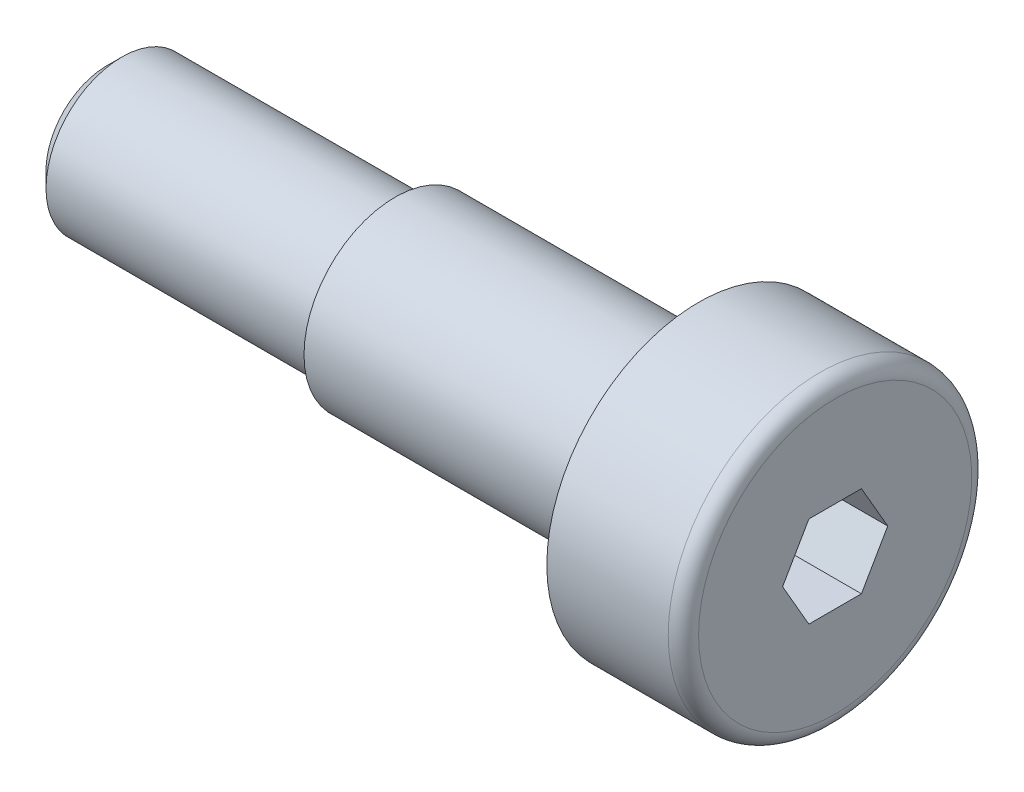
SolidWorks part; units mm, degrees
material "AISI 1020"
ref_plane "XY (Front)" through (0, 0, 0) normal (0, 0, 1) x (1, 0, 0)
ref_plane "XZ (Top)" through (0, 0, 0) normal (0, 1, 0) x (1, 0, 0)
ref_plane "YZ (Right)" through (0, 0, 0) normal (1, 0, 0) x (0, 0, -1)
ref_axis "X" through (-25.2, 0, 0) along (1, 0, 0)
ref_axis "Y" through (0, 5.5, 0) along (0, -1, 0)
ref_axis "Z" through (0, 0, -5.5) along (0, 0, 1)
sketch "Sketch1" plane through (0, 0, 0) normal (0, 0, 1) x (1, 0, 0)
  line L0 (0, 0) -> (0, 4.5)
  line L1 (-0.5, 5) -> (-4.5, 5)
  line L2 (-4.5, 5) -> (-4.5, 3)
  line L3 (-4.5, 3) -> (-14.5, 3)
  line L4 (-14.5, 3) -> (-14.5, 2.5)
  line L5 (-14.5, 2.5) -> (-24, 2.5)
  line L6 (-24, 2.5) -> (-24, 0)
  line L7 (-24, 0) -> (0, 0)
  line L8 (0, 0) -> (5.7531, 0) construction
  arc A0 (0, 4.5) -> (-0.5, 5) centre (-0.5, 4.5) ccw
  dimension "R" = 0.5
  dimension "d3" = 10
  dimension "d1" = 6
  dimension "M" = 5
  dimension "l3" = 4.5
  dimension "l1" = 10
  dimension "l2" = 9.5
revolve "Revolve1" add sketch "Sketch1" angle 360 about L8
cosmetic thread "Cosmetic Thread1" parameters "D2"=4.2
chamfer "Chamfer1" distance 0.5 angle 45 1 edges at (-24, 0, 2.5)
sketch "Sketch2" plane through (0, 0, 0) normal (1, 0, 0) x (0, 0, -1)
  line L1 (1.7321, 0) -> (0.866, 1.5)
  line L2 (0.866, 1.5) -> (-0.866, 1.5)
  line L3 (-0.866, 1.5) -> (-1.7321, 0)
  line L4 (-1.7321, 0) -> (-0.866, -1.5)
  line L5 (-0.866, -1.5) -> (0.866, -1.5)
  line L6 (0.866, -1.5) -> (1.7321, 0)
  circle A0 centre (0, 0) radius 1.5 construction
  dimension "AF" = 3
extrude "Cut-Extrude1" cut sketch "Sketch2" against normal blind 2.4
